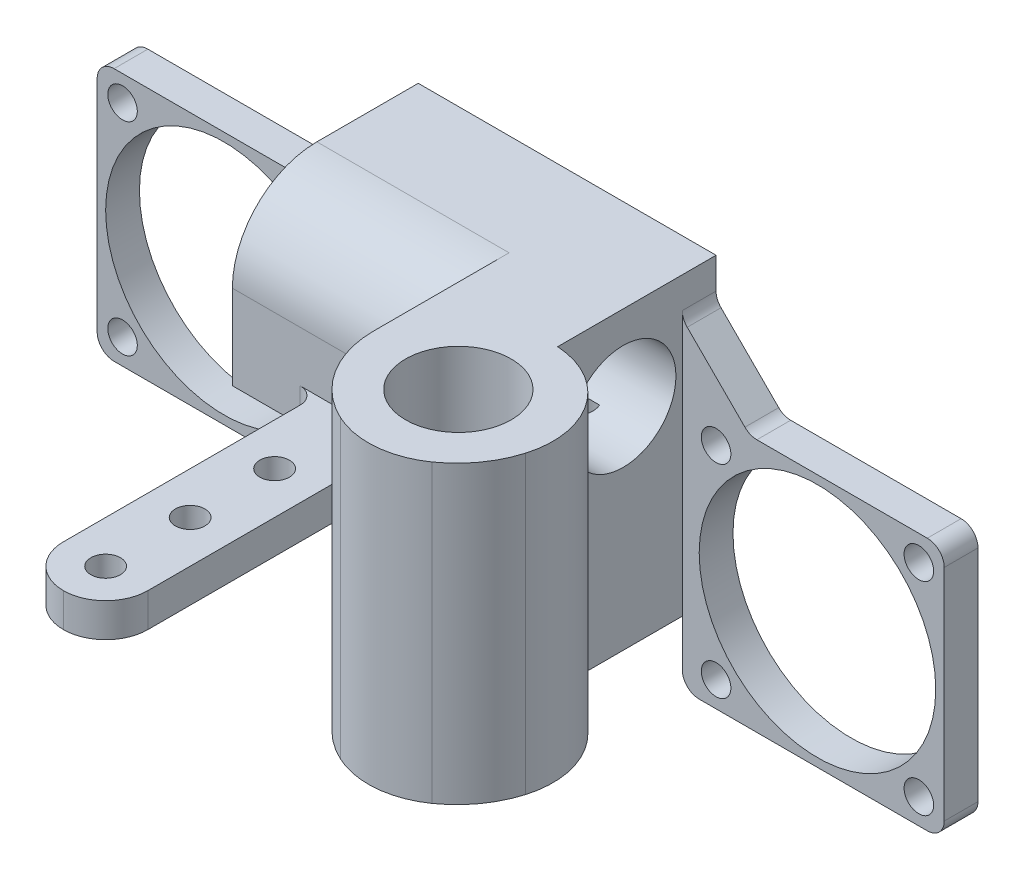
SolidWorks part; units mm, degrees
ref_plane "Спереди" through (0, 0, 0) normal (0, 0, 1) x (1, 0, 0)
ref_plane "Сверху" through (0, 0, 0) normal (0, 1, 0) x (1, 0, 0)
ref_plane "Справа" through (0, 0, 0) normal (1, 0, 0) x (0, 0, -1)
ref_plane "Плоскость4" through (0, 35, 0) normal (0, 1, 0) x (1, 0, 0)
sketch "Эскиз1" plane through (0, 35, 0) normal (0, 1, 0) x (1, 0, 0)
  line L0 (35, 0) -> (13, 0)
  line L1 (13, 0) -> (13, -28)
  line L2 (35, -28.1678) -> (35, 0)
  arc A0 (13, -28) -> (25, -40) centre (25, -28) ccw
  arc A1 (25, -40) -> (35, -28.1678) centre (23, -28.1678) ccw
extrude "Бобышка-Вытянуть1" add sketch "Эскиз1" against normal blind 35
sketch "Эскиз2" plane through (13, 0, 0) normal (-1, 0, 0) x (0, 0, 1)
  line L0 (22, 0) -> (0, 0)
  line L1 (0, 0) -> (0, 35)
  line L2 (0, 35) -> (22, 35)
  line L3 (22, 35) -> (22, 0)
extrude "Бобышка-Вытянуть2" add sketch "Эскиз2" along normal blind 22.75
sketch "Эскиз3" plane through (-9.75, 0, 0) normal (-1, 0, 0) x (0, 0, 1)
  line L0 (11, 15) -> (0, 15)
  line L1 (0, 15) -> (0, 0)
  line L2 (0, 0) -> (11, 0)
  line L3 (11, 0) -> (11, 15)
  dimension "D1" = 20
  dimension "D2" = 15
  dimension "D3" = 11
extrude "Вырез-Вытянуть1" cut sketch "Эскиз3" against normal blind 32
hole_wizard "Диаметр отверстия Ø12.5 (12.5)1" positions "Эскиз5" profile "Эскиз4" hole size "Ø12.5" standard "Ansi Metric"
sketch "Эскиз5" plane through (0, 35, 0) normal (0, 1, 0) x (1, 0, 0)
  point P0 (24, -29)
sketch "Эскиз4" plane through (24, 35, 29) normal (1, 0, 0) x (0, 0, 1)
  line L0 (0, 0) -> (0, 35)
  line L1 (0, 35) -> (6.25, 35)
  line L2 (6.25, 35) -> (6.25, 0)
  line L5 (6.25, 0) -> (0, 0)
  line L11 (0, -6.35) -> (0, 107.95) construction
  dimension "Диаметр сквозного отверстия" = 12.5
  dimension "Глубина сквозного отверстия" = 35
hole_wizard "Диаметр отверстия Ø12.5 (12.5)2" positions "Эскиз7" profile "Эскиз6" hole size "Ø12.5" standard "Ansi Metric"
sketch "Эскиз7" plane through (35, 0, 0) normal (1, 0, 0) x (0, 0, -1)
  line L0 (55, 35) -> (-55, 35) construction
  point P0 (-11, 25)
  dimension "D1" = 10
sketch "Эскиз6" plane through (35, 25, 11) normal (0, 1, 0) x (0, 0, -1)
  line L0 (0, 0) -> (0, 44.75)
  line L1 (0, 44.75) -> (6.25, 44.75)
  line L2 (6.25, 44.75) -> (6.25, 0)
  line L5 (6.25, 0) -> (0, 0)
  line L11 (0, -6.35) -> (0, 107.95) construction
  dimension "Диаметр сквозного отверстия" = 12.5
  dimension "Глубина сквозного отверстия" = 44.75
hole_wizard "Диаметр отверстия Ø3.5 (3.5)1" positions "Эскиз9" profile "Эскиз8" hole size "Ø3.5" standard "Ansi Metric"
sketch "Эскиз9" plane through (0, 15, 0) normal (0, -1, 0) x (-1, 0, 0)
  line L0 (9.75, -11) -> (9.75, 0) construction
  point P0 (-17.25, -7)
  point P1 (6.75, -7)
  point P2 (-12.25, -7)
  point P3 (1.75, -7)
  dimension "D1" = 3
  dimension "D2" = 5
  dimension "D3" = 14
  dimension "D4" = 5
sketch "Эскиз8" plane through (17.25, 15, 7) normal (1, 0, 0) x (0, 0, -1)
  line L0 (0, 0) -> (0, 5)
  line L1 (0, 5) -> (1.75, 5)
  line L2 (1.75, 5) -> (1.75, 0)
  line L5 (1.75, 0) -> (0, 0)
  line L10 (0, 5) -> (-1.75, 5) construction
  line L11 (0, -6.35) -> (0, 107.95) construction
  dimension "Диаметр отверстия" = 3.5
  dimension "Глубина отверстия" = 5
  dimension "Угол заточки сверла" = 180
sketch "Эскиз10" plane through (0, 0, 0) normal (0, -1, 0) x (1, 0, 0)
  line L1 (35, 0) -> (25.5, 0)
  line L2 (35, 0) -> (35, 18.75)
  line L3 (35, 18.75) -> (25.5, 18.75)
  line L4 (25.5, 0) -> (25.5, 18.75)
  circle A0 centre (24, 29) radius 6.25 construction
  dimension "D1" = 9.5
  dimension "D2" = 10.25
extrude "Вырез-Вытянуть2" cut sketch "Эскиз10" against normal through all
sketch "Эскиз11" plane through (0, 0, 0) normal (0, -1, 0) x (1, 0, 0)
  line L0 (22.25, 11) -> (-9.75, 11) construction
  line L1 (-9.75, 11) -> (13, 11)
  line L2 (-9.75, 11) -> (-9.75, 22)
  line L3 (-9.75, 22) -> (13, 22)
  line L4 (13, 11) -> (13, 22)
  line L5 (-9.75, 22) -> (13, 22) construction
  line L6 (-9.75, 11) -> (-9.75, 22) construction
  dimension "D1" = 0
  dimension "D2" = 0
extrude "Вырез-Вытянуть3" cut sketch "Эскиз11" against normal up to surface (15 mm away) up to face at (17.25, 15, 5.25)
fillet "Скругление2" radius 10 1 edges at (25, 17.5, 40)
sketch "Эскиз13" plane through (25.5, 0, 0) normal (1, 0, 0) x (0, 0, -1)
  line L12 (-4, -7.5) -> (0, -7.5)
  line L13 (-4, -7.5) -> (-4, 22.5)
  line L14 (-4, 22.5) -> (0, 22.5)
  line L15 (0, -7.5) -> (0, 22.5)
  circle A1 centre (-11, 25) radius 6.25 construction
  dimension "D1" = 30
  dimension "D3" = 7
  dimension "D4" = 4
extrude "Бобышка-Вытянуть3" add sketch "Эскиз13" along normal blind 31 separate body
hole_wizard "Диаметр отверстия Ø3.5 (3.5)2" positions "Эскиз15" profile "Эскиз16" hole size "Ø3.5" standard "ISO" end condition through all
sketch "Эскиз15" plane through (0, 0, 4) normal (0, 0, 1) x (1, 0, 0)
  line L0 (56.5, -7.5) -> (25.5, -7.5) construction
  line L1 (56.5, 22.5) -> (25.5, 22.5) construction
  line L2 (25.5, 22.5) -> (25.5, -7.5) construction
  line L3 (56.5, 22.5) -> (56.5, -7.5) construction
  point P0 (29.5, -4.5)
  point P2 (29.5, 19.5)
  point P4 (53.5, 19.5)
  point P6 (53.5, -4.5)
  dimension "D1" = 3
  dimension "D2" = 3
  dimension "D3" = 4
  dimension "D4" = 4
  dimension "D5" = 3
  dimension "D6" = 3
  dimension "D7" = 3
  dimension "D8" = 3
sketch "Эскиз16" plane through (29.5, -4.5, 4) normal (1, 0, 0) x (0, -1, 0)
  line L0 (0, 0) -> (0, 4)
  line L1 (0, 4) -> (1.75, 4)
  line L2 (1.75, 4) -> (1.75, 0)
  line L5 (1.75, 0) -> (0, 0)
  line L11 (0, -6.35) -> (0, 107.95) construction
  dimension "Диаметр сквозного отверстия" = 3.5
  dimension "Глубина сквозного отверстия" = 4
sketch "Эскиз17" plane through (0, 0, 4) normal (0, 0, 1) x (1, 0, 0)
  line L0 (56.5, 22.5) -> (56.5, -7.5) construction
  line L3 (56.5, -7.5) -> (25.5, -7.5) construction
  circle A0 centre (41.5, 7.5) radius 14
  dimension "D1" = 28
  dimension "D2" = 15
  dimension "D3" = 15
extrude "Вырез-Вытянуть4" cut sketch "Эскиз17" against normal through all
sketch "Эскиз19" plane through (-9.75, 0, 0) normal (-1, 0, 0) x (0, 0, 1)
  line L0 (0, 35) -> (0, 15) construction
  line L1 (4, 22.5) -> (0, 22.5)
  line L2 (4, 22.5) -> (4, -7.5)
  line L3 (4, -7.5) -> (0, -7.5)
  line L4 (0, 22.5) -> (0, -7.5)
  dimension "D3" = 0
  dimension "D1" = 4
  dimension "D2" = 30
extrude "Бобышка-Вытянуть5" add sketch "Эскиз19" along normal blind 34
sketch "Эскиз20" plane through (0, 0, 4) normal (0, 0, 1) x (1, 0, 0)
  line L0 (-43.75, -7.5) -> (-43.75, 22.5) construction
  line L2 (-43.75, -7.5) -> (-9.75, -7.5) construction
  circle A0 centre (-28.75, 7.5) radius 14
  dimension "D1" = 15
  dimension "D2" = 15
extrude "Вырез-Вытянуть5" cut sketch "Эскиз20" against normal through all
hole_wizard "Диаметр отверстия Ø3.5 (3.5)3" positions "Эскиз21" profile "Эскиз22" hole size "Ø3.5" standard "ISO" end condition through all
sketch "Эскиз21" plane through (0, 0, 4) normal (0, 0, 1) x (1, 0, 0)
  line L0 (-9.75, 15) -> (-9.75, 22.5) construction
  line L1 (-9.75, -7.5) -> (-9.75, 15) construction
  line L2 (-43.75, 22.5) -> (-9.75, 22.5) construction
  line L3 (-43.75, -7.5) -> (-9.75, -7.5) construction
  line L5 (-43.75, -7.5) -> (-43.75, 22.5) construction
  point P0 (-16.75, 19.5)
  point P2 (-16.75, -4.5)
  point P4 (-40.75, -4.5)
  point P6 (-40.75, 19.5)
  dimension "D1" = 7
  dimension "D2" = 7
  dimension "D3" = 3
  dimension "D4" = 3
  dimension "D5" = 3
  dimension "D6" = 3
  dimension "D7" = 3
  dimension "D8" = 3
sketch "Эскиз22" plane through (-16.75, 19.5, 4) normal (1, 0, 0) x (0, -1, 0)
  line L0 (0, 0) -> (0, 4)
  line L1 (0, 4) -> (1.75, 4)
  line L2 (1.75, 4) -> (1.75, 0)
  line L5 (1.75, 0) -> (0, 0)
  line L11 (0, -6.35) -> (0, 107.95) construction
  dimension "Диаметр сквозного отверстия" = 3.5
  dimension "Глубина сквозного отверстия" = 4
sketch "Эскиз24" plane through (0, 0, 4) normal (0, 0, 1) x (1, 0, 0)
  line L0 (-9.75, 30.5) -> (-17.75, 22.5)
  line L1 (-9.75, 22.5) -> (-17.75, 22.5)
  line L2 (-9.75, 22.5) -> (-9.75, 30.5)
extrude "Бобышка-Вытянуть6" add sketch "Эскиз24" against normal up to surface (4 mm away) up to face at (-15, 19.5, 0)
sketch "Эскиз25" plane through (0, 0, 4) normal (0, 0, 1) x (1, 0, 0)
  line L0 (33.5, 22.5) -> (25.5, 30.5)
  line L1 (25.5, 22.5) -> (33.5, 22.5)
  line L2 (25.5, 22.5) -> (25.5, 30.5)
extrude "Бобышка-Вытянуть7" add sketch "Эскиз25" against normal up to surface (4 mm away) up to face at (55.5, 7.5, 0)
sketch "Эскиз26" plane through (0, 0, 22) normal (0, 0, 1) x (1, 0, 0)
  line L0 (13, 15) -> (-9.75, 15) construction
  line L1 (0.25, 15) -> (10.25, 15)
  line L2 (0.25, 15) -> (0.25, 19)
  line L3 (0.25, 19) -> (10.25, 19)
  line L4 (10.25, 15) -> (10.25, 19)
  line L6 (-9.75, 15) -> (-9.75, 35) construction
  dimension "D1" = 10
  dimension "D2" = 10
  dimension "D3" = 4
extrude "Бобышка-Вытянуть8" add sketch "Эскиз26" along normal blind 35
hole_wizard "Диаметр отверстия Ø3.5 (3.5)4" positions "Эскиз28" profile "Эскиз29" hole size "Ø3.5" standard "ISO" end condition through all
sketch "Эскиз28" plane through (0, 15, 0) normal (0, -1, 0) x (-1, 0, 0)
  line L0 (-0.25, -57) -> (-0.25, -22) construction
  line L2 (-0.25, -57) -> (-10.25, -57) construction
  point P0 (-5.25, -52)
  point P25 (-5.25, -42)
  point P27 (-5.25, -32)
  dimension "D1" = 5
  dimension "D2" = 5
  dimension "D3" = 3
sketch "Эскиз29" plane through (5.25, 15, 52) normal (1, 0, 0) x (0, 0, -1)
  line L0 (0, 0) -> (0, 20)
  line L1 (0, 20) -> (1.75, 20)
  line L2 (1.75, 20) -> (1.75, 0)
  line L5 (1.75, 0) -> (0, 0)
  line L11 (0, -6.35) -> (0, 107.95) construction
  dimension "Диаметр сквозного отверстия" = 3.5
  dimension "Глубина сквозного отверстия" = 20
fillet "Скругление7" radius 2 2 edges at (10.25, 17, 22) (0.25, 17, 22)
fillet "Скругление9" radius 5 2 edges at (0.25, 17, 57) (10.25, 17, 57)
fillet "Скругление10" radius 10 1 edges at (35, 17.5, 18.75)
fillet "Скругление12" radius 10 1 edges at (1.625, 35, 22)
fillet "Скругление13" radius 2 5 edges at (-9.75, -7.5, 2) (-43.75, -7.5, 2) (-43.75, 22.5, 2) (-17.75, 22.5, 2) (-9.75, 30.5, 2)
fillet "Скругление14" radius 2 5 edges at (25.5, 30.5, 2) (33.5, 22.5, 2) (56.5, 22.5, 2) (56.5, -7.5, 2) (25.5, -7.5, 2)
sketch "Эскиз32" plane through (0, 0, 4) normal (0, 0, 1) x (1, 0, 0)
  line L0 (-9.75, -5.5) -> (-9.75, 15) construction
  line L1 (-9.75, 15) -> (-9.75, 31.3284) construction
  line L2 (-9.75, 2.2703) -> (-9.75, 15)
  arc A0 (-9.75, 15) -> (-9.75, 2.2703) centre (6.4963, 8.6352) ccw
extrude "Вырез-Вытянуть6" cut sketch "Эскиз32" against normal through all
